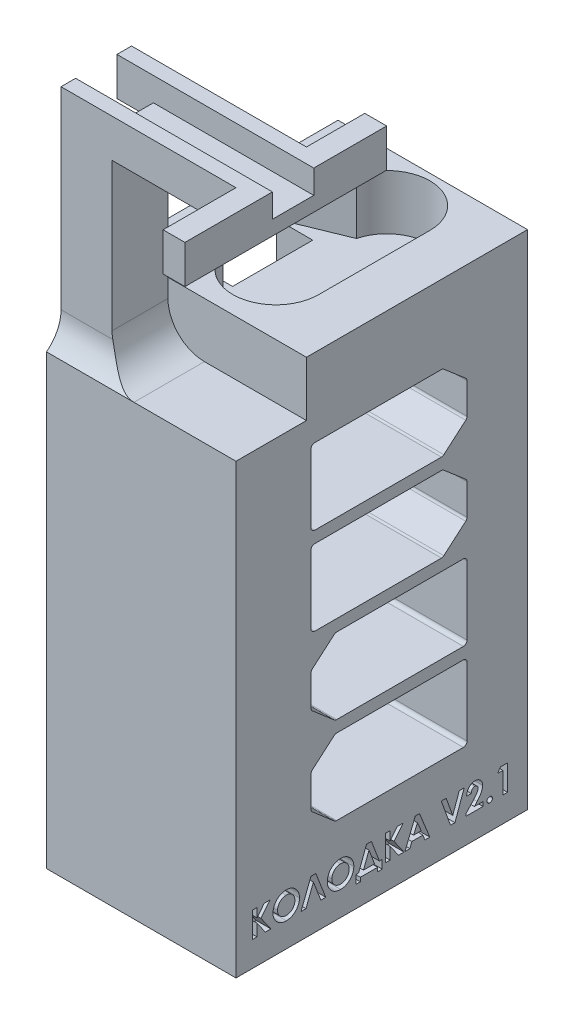
SolidWorks part; units mm, degrees
material "ABS"
ref_plane "Спереди" through (0, 0, 0) normal (0, 0, 1) x (1, 0, 0)
ref_plane "Сверху" through (0, 0, 0) normal (0, 1, 0) x (1, 0, 0)
ref_plane "Справа" through (0, 0, 0) normal (1, 0, 0) x (0, 0, -1)
sketch "Эскиз1" plane through (0, 0, 0) normal (1, 0, 0) x (0, 0, -1)
  line L0 (-20, 26.2) -> (-20, -26.2)
  line L1 (20, 26.2) -> (20, -26.2)
  line L2 (-20, -26.2) -> (20, -26.2)
  line L3 (-20, 23.2) -> (20, 23.2) construction
  line L4 (11.7, -10.9) -> (11.7, -1.5)
  line L5 (-6.1888, -11.4) -> (11.2, -11.4)
  line L6 (-9.5259, -8.6915) -> (-6.5147, -11.2792)
  line L7 (-9.7, -4.0877) -> (-9.7, -8.3123)
  line L8 (-6.5147, -1.1208) -> (-9.5259, -3.7085)
  line L9 (11.2, -1) -> (-6.1888, -1)
  line L10 (11.7, -22.9) -> (11.7, -13.5)
  line L11 (-6.1888, -23.4) -> (11.2, -23.4)
  line L12 (-9.5259, -20.6915) -> (-6.5147, -23.2792)
  line L13 (-9.7, -16.0877) -> (-9.7, -20.3123)
  line L14 (-6.5147, -13.1208) -> (-9.5259, -15.7085)
  line L15 (11.2, -13) -> (-6.1888, -13)
  line L16 (-9.7, 10.5) -> (-9.7, 1.1)
  line L17 (8.1888, 11) -> (-9.2, 11)
  line L18 (-9.7, 22.5) -> (-9.7, 13.1)
  line L19 (8.1888, 23) -> (-9.2, 23)
  line L20 (11.5259, 20.2915) -> (8.5147, 22.8792)
  line L21 (11.7, 15.6877) -> (11.7, 19.9123)
  line L22 (11.5259, 8.2915) -> (8.5147, 10.8792)
  line L23 (11.7, 3.6877) -> (11.7, 7.9123)
  line L24 (8.5147, 0.7208) -> (11.5259, 3.3085)
  line L25 (-9.2, 0.6) -> (8.1888, 0.6)
  line L26 (8.5147, 12.7208) -> (11.5259, 15.3085)
  line L27 (-9.2, 12.6) -> (8.1888, 12.6)
  line L28 (-20, 26.2) -> (20, 26.2)
  arc A0 (11.7, -1.5) -> (11.2, -1) centre (11.2, -1.5) ccw
  arc A1 (11.2, -11.4) -> (11.7, -10.9) centre (11.2, -10.9) ccw
  arc A2 (-6.5147, -11.2792) -> (-6.1888, -11.4) centre (-6.1888, -10.9) ccw
  arc A3 (-9.7, -8.3123) -> (-9.5259, -8.6915) centre (-9.2, -8.3123) ccw
  arc A4 (-9.5259, -3.7085) -> (-9.7, -4.0877) centre (-9.2, -4.0877) ccw
  arc A5 (-6.1888, -1) -> (-6.5147, -1.1208) centre (-6.1888, -1.5) ccw
  arc A6 (11.7, -13.5) -> (11.2, -13) centre (11.2, -13.5) ccw
  arc A7 (11.2, -23.4) -> (11.7, -22.9) centre (11.2, -22.9) ccw
  arc A8 (-6.5147, -23.2792) -> (-6.1888, -23.4) centre (-6.1888, -22.9) ccw
  arc A9 (-9.7, -20.3123) -> (-9.5259, -20.6915) centre (-9.2, -20.3123) ccw
  arc A10 (-9.5259, -15.7085) -> (-9.7, -16.0877) centre (-9.2, -16.0877) ccw
  arc A11 (-6.1888, -13) -> (-6.5147, -13.1208) centre (-6.1888, -13.5) ccw
  arc A12 (-9.7, 1.1) -> (-9.2, 0.6) centre (-9.2, 1.1) ccw
  arc A13 (-9.2, 11) -> (-9.7, 10.5) centre (-9.2, 10.5) ccw
  arc A14 (-9.7, 13.1) -> (-9.2, 12.6) centre (-9.2, 13.1) ccw
  arc A15 (-9.2, 23) -> (-9.7, 22.5) centre (-9.2, 22.5) ccw
  arc A16 (8.5147, 22.8792) -> (8.1888, 23) centre (8.1888, 22.5) ccw
  arc A17 (11.7, 19.9123) -> (11.5259, 20.2915) centre (11.2, 19.9123) ccw
  arc A18 (8.5147, 10.8792) -> (8.1888, 11) centre (8.1888, 10.5) ccw
  arc A19 (11.7, 7.9123) -> (11.5259, 8.2915) centre (11.2, 7.9123) ccw
  arc A20 (11.5259, 3.3085) -> (11.7, 3.6877) centre (11.2, 3.6877) ccw
  arc A21 (8.1888, 0.6) -> (8.5147, 0.7208) centre (8.1888, 1.1) ccw
  arc A22 (11.5259, 15.3085) -> (11.7, 15.6877) centre (11.2, 15.6877) ccw
  arc A23 (8.1888, 12.6) -> (8.5147, 12.7208) centre (8.1888, 13.1) ccw
extrude "Бобышка-Вытянуть1" add sketch "Эскиз1" along normal blind 26
sketch "Эскиз2" plane through (0, 0, 0) normal (-1, 0, 0) x (0, 0, 1)
  line L6 (-0.535, 17.8) -> (-0.535, -18.2)
  line L7 (9.535, -18.2) -> (9.535, 17.8)
  arc A6 (9.535, 17.8) -> (-0.535, 17.8) centre (4.5, 17.8) ccw
  arc A7 (-0.535, -18.2) -> (9.535, -18.2) centre (4.5, -18.2) ccw
extrude "Вырез-Вытянуть1" cut sketch "Эскиз2" against normal blind 5
sketch "Эскиз3" plane through (0, 0, 0) normal (-1, 0, 0) x (0, 0, 1)
  line L13 (-1.465, 5.8) -> (-1.465, 26.4)
  line L14 (-1.465, 26.4) -> (-11.535, 26.4)
  line L15 (-11.535, 26.4) -> (-11.535, 5.8)
  arc A3 (-11.535, 5.8) -> (-1.465, 5.8) centre (-6.5, 5.8) ccw
extrude "Вырез-Вытянуть2" cut sketch "Эскиз3" against normal blind 5
sketch "Эскиз4" plane through (0, -26.2, 0) normal (0, -1, 0) x (1, 0, 0)
  line L1 (0, 20) -> (26, 20)
  line L2 (0, 20) -> (0, -20)
  line L3 (0, -20) -> (26, -20)
  line L4 (26, 20) -> (26, -20)
extrude "Бобышка-Вытянуть2" add sketch "Эскиз4" along normal blind 9
sketch "Эскиз5" plane through (0, 0, 0) normal (-1, 0, 0) x (0, 0, 1)
  line L0 (-0.535, 12.6) -> (-1.465, 12.6) construction
  line L1 (-1.465, 12.6) -> (-0.535, 12.6)
  line L2 (-1.465, 12.6) -> (-1.465, 11)
  line L3 (-1.465, 11) -> (-0.535, 11)
  line L4 (-0.535, 12.6) -> (-0.535, 11)
  line L5 (-1.465, 11) -> (-1.465, 12.6) construction
  line L6 (-1.465, 11) -> (-0.535, 11) construction
extrude "Вырез-Вытянуть3" cut sketch "Эскиз5" against normal blind 5
sketch "Эскиз6" plane through (26, 0, 0) normal (1, 0, 0) x (0, 0, -1)
  line L3 (-20, -31.7619) -> (20, -31.7619) construction
  text T0 "<b>КОЛОДКА V2.1</b>"
  point P9 (-2.1603, -29.3)
extrude "Вырез-Вытянуть4" cut sketch "Эскиз6" against normal blind 2
sketch "Эскиз7" plane through (0, 0, 0) normal (-1, 0, 0) x (0, 0, 1)
  line L1 (-11.535, 26.2) -> (-0.535, 26.2)
  line L2 (-11.535, 26.2) -> (-11.535, -13)
  line L3 (-11.535, -13) -> (-0.535, -13)
  line L4 (-0.535, 26.2) -> (-0.535, -13)
extrude "Вырез-Вытянуть5" cut sketch "Эскиз7" against normal blind 5
sketch "Эскиз8" plane through (0, 0, 0) normal (-1, 0, 0) x (0, 0, 1)
  line L0 (-11.535, -30.4) -> (-11.535, -20.6033)
  line L5 (-11.535, -20.6033) -> (-1.465, -20.6033)
  line L6 (-1.465, -30.4) -> (-1.465, -20.6033)
  line L7 (-11.535, -30.4) -> (-1.465, -30.4)
extrude "Вырез-Вытянуть6" cut sketch "Эскиз8" against normal blind 5
sketch "Эскиз9" plane through (0, 0, 0) normal (-1, 0, 0) x (0, 0, 1)
  line L0 (-0.535, 26.2) -> (20, 26.2) construction
  line L1 (-10.835, -24.53) -> (-3.431, -24.53)
  line L2 (-10.835, -24.53) -> (-10.835, -33.2)
  line L3 (-10.835, -33.2) -> (-3.431, -33.2)
  line L5 (-3.431, -33.2) -> (19, -33.2)
  line L7 (-3.431, -24.53) -> (10.33, -24.53)
  line L8 (19, -33.2) -> (19, -24.53)
  line L10 (19, -24.53) -> (19, 26.2)
  line L11 (19, 26.2) -> (10.33, 26.2)
  line L12 (10.33, -24.53) -> (10.33, 26.2)
  line L13 (20, 26.2) -> (20, -35.2) construction
  line L14 (20, -35.2) -> (-20, -35.2) construction
  dimension "D1" = 8.67
  dimension "D2" = 1
  dimension "D3" = 8.67
  dimension "D4" = 2
extrude "Вырез-Вытянуть7" cut sketch "Эскиз9" against normal blind 5
sketch "Эскиз10" plane through (0, 26.2, 0) normal (0, 1, 0) x (1, 0, 0)
  line L12 (26, 20) -> (0, 20) construction
  line L13 (0, -10.33) -> (26, -10.33)
  line L14 (0, -10.33) -> (0, 0.535)
  line L15 (0, 20) -> (26, 20)
  line L16 (26, -10.33) -> (26, 20)
  line L17 (26, 20) -> (26, -20) construction
  line L23 (0, 11.535) -> (0, 20)
  line L32 (7.8, 14.7252) -> (0, 11.535)
  line L33 (7.8, -3.5582) -> (0, 0.535)
  line L34 (19.4, -2.035) -> (19.4, 13.202)
  line L36 (5, 0.535) -> (0, 0.535) construction
  arc A12 (7.8, -3.5582) -> (19.4, -2.035) centre (13.5, -2.035) ccw
  arc A13 (19.4, 13.202) -> (7.8, 14.7252) centre (13.5, 13.202) ccw
extrude "Бобышка-Вытянуть3" add sketch "Эскиз10" along normal up to surface (7.52 mm away)
sketch "Эскиз12" plane through (5, 0, 0) normal (-1, 0, 0) x (0, 0, 1)
  line L0 (19, 26.2) -> (10.33, 26.2) construction
  line L1 (16, 26.2) -> (19, 26.2)
  line L2 (16, 26.2) -> (16, -33.2)
  line L3 (16, -33.2) -> (19, -33.2)
  line L4 (19, 26.2) -> (19, -33.2)
  line L5 (19, -33.2) -> (19, 26.2) construction
extrude "Бобышка-Вытянуть4" add sketch "Эскиз12" along normal blind 5
sketch "Эскиз13" plane through (0, 26.2, 0) normal (0, 1, 0) x (1, 0, 0)
  line L0 (0, -16) -> (5, -16) construction
  line L1 (5, -16) -> (0, -16)
  line L3 (7, -18) -> (0, -18)
  line L4 (0, -16) -> (0, -18)
  line L5 (5, -10.33) -> (5, -16)
  line L6 (5, -10.33) -> (26, -10.33) construction
  line L7 (5, -16) -> (5, -10.33) construction
  line L8 (7, -10.33) -> (7, -18)
  line L9 (5, -10.33) -> (5, -18) construction
  line L10 (5, -10.33) -> (7, -10.33)
  dimension "D1" = 2
  dimension "D2" = 2
extrude "Бобышка-Вытянуть5" add sketch "Эскиз13" along normal up to surface (27.25 mm away)
fillet "Скругление1" radius 5 2 edges at (7, 26.2, 14.165) (3.5, 26.2, 18)
sketch "Эскиз14" plane through (0, 0, 16) normal (0, 0, 1) x (1, 0, 0)
  line L1 (0, 56.7) -> (27, 56.7)
  line L2 (0, 56.7) -> (0, 53.45)
  line L3 (0, 53.45) -> (27, 53.45)
  line L4 (27, 56.7) -> (27, 53.45)
extrude "Бобышка-Вытянуть6" add sketch "Эскиз14" along normal blind 2
sketch "Эскиз15" plane through (27, 0, 0) normal (-1, 0, 0) x (0, 0, 1)
  line L1 (18, 56.7) -> (28, 56.7)
  line L2 (18, 56.7) -> (18, 51.45)
  line L3 (18, 51.45) -> (28, 51.45)
  line L4 (28, 56.7) -> (28, 51.45)
  line L5 (10.33, 56.7) -> (0.33, 56.7)
  line L6 (10.33, 56.7) -> (10.33, 51.45)
  line L7 (10.33, 51.45) -> (0.33, 51.45)
  line L8 (0.33, 56.7) -> (0.33, 51.45)
  dimension "D1" = 10
  dimension "D2" = 5.25
  dimension "D3" = 10
  dimension "D4" = 5.25
extrude "Бобышка-Вытянуть7" add sketch "Эскиз15" along normal blind 3
sketch "Эскиз16" plane through (0, 53.45, 0) normal (0, -1, 0) x (1, 0, 0)
  line L0 (7, 18) -> (7, 16) construction
  line L2 (7, 16) -> (7, 10.33)
  line L3 (7, 10.33) -> (27, 10.33)
  line L4 (27, 16) -> (27, 10.33)
  line L5 (7, 16) -> (27, 16) construction
  line L8 (7, 18) -> (24, 18) construction
  line L11 (27, 16) -> (27, 18)
  line L12 (27, 18) -> (7, 18)
  line L13 (7, 16) -> (7, 18)
extrude "Бобышка-Вытянуть9" add sketch "Эскиз16" along normal blind 2
sketch "Эскиз17" plane through (0, 0, 10.33) normal (0, 0, -1) x (-1, 0, 0)
  line L0 (-24, 51.45) -> (-24, 53.45) construction
  line L1 (-24, 51.45) -> (0, 51.45)
  line L2 (-24, 51.45) -> (-24, 56.7)
  line L3 (-24, 56.7) -> (0, 56.7)
  line L4 (0, 51.45) -> (0, 56.7)
  line L5 (-7, 51.45) -> (-24, 51.45) construction
extrude "Бобышка-Вытянуть10" add sketch "Эскиз17" along normal blind 2
